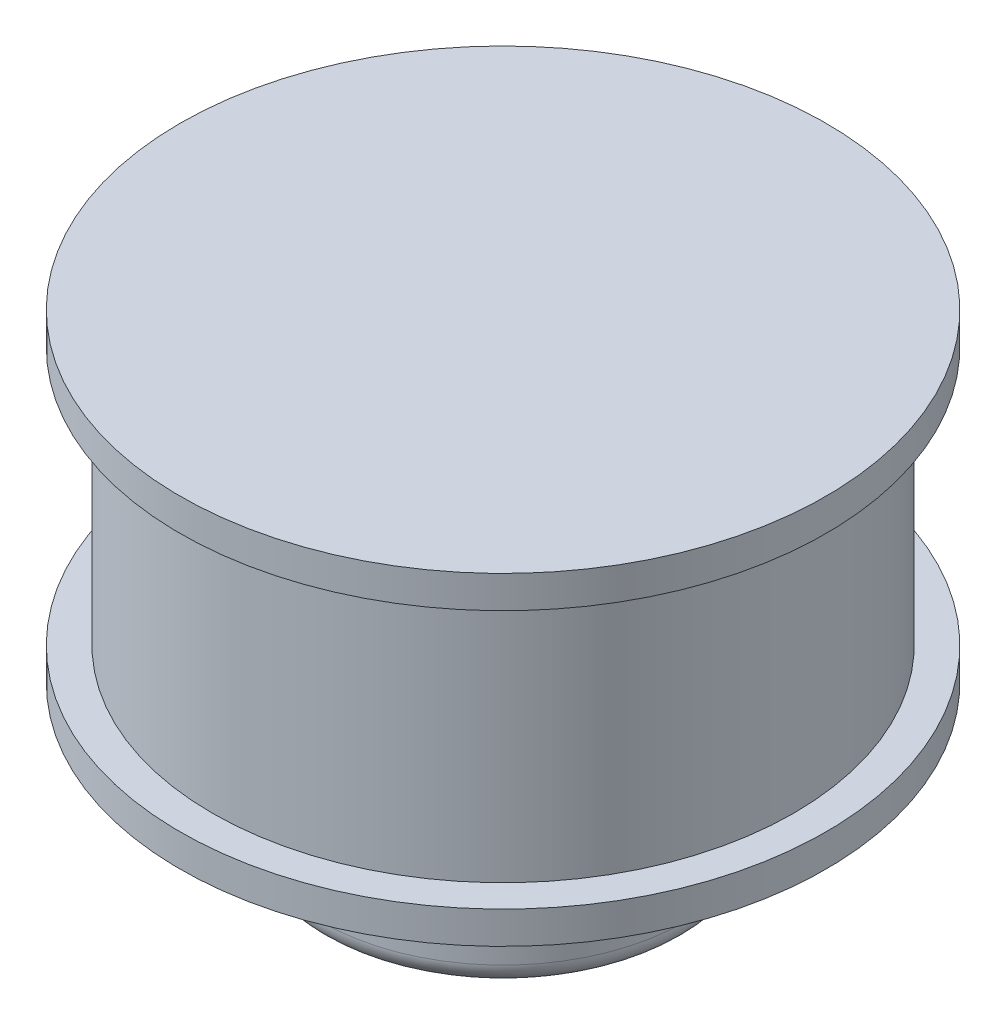
SolidWorks part; units mm, degrees
material "ABS"
ref_plane "Front Plane" through (0, 0, 0) normal (0, 0, 1) x (1, 0, 0)
ref_plane "Top Plane" through (0, 0, 0) normal (0, 1, 0) x (1, 0, 0)
ref_plane "Right Plane" through (0, 0, 0) normal (1, 0, 0) x (0, 0, -1)
sketch "Sketch1" plane through (0, 0, 0) normal (0, 0, 1) x (1, 0, 0)
  line L2 (-8.5, -6.35) -> (-8.5, 0)
  line L3 (-8.5, 0) -> (-15, 0)
  line L4 (-15, 0) -> (-15, 1.5)
  line L5 (-15, 1.5) -> (-13.5, 1.5)
  line L6 (-13.5, 1.5) -> (-13.5, 13.5)
  line L7 (-13.5, 13.5) -> (-15, 13.5)
  line L8 (-15, 13.5) -> (-15, 15)
  line L9 (-15, 15) -> (0, 15)
  line L10 (0, 15) -> (0, 7.65)
  line L11 (-4, -6.35) -> (-8.5, -6.35)
  line L12 (-4, 7.65) -> (-4, -6.35)
  line L13 (0, 7.65) -> (-4, 7.65)
  dimension "D1" = 8.5
  dimension "D2" = 1.5
  dimension "D3" = 6.35
  dimension "D4" = 1.5
  dimension "D5" = 4
  dimension "D6" = 14
  dimension "D7" = 15
  dimension "D8" = 15
revolve "Revolve1" add sketch "Sketch1" angle 360 about L10
fillet "Fillet1" radius 1 2 edges at (-8.5, -6.35, 0) (-4, -6.35, 0)
hole_wizard "M3x0.5 Tapped Hole1" positions "Sketch2" profile "Sketch3" tap size "M3x0.5" standard "ANSI Metric" end condition up to next
sketch "Sketch2" plane through (0, 0, 0) normal (0, 0, 1) x (1, 0, 0)
  line L0 (-7.5, -6.35) -> (7.5, -6.35) construction
  point P0 (0, -2.35)
  dimension "D1" = 4
sketch "Sketch3" plane through (0, -2.35, 0) normal (1, 0, 0) x (0, 1, 0)
  line L0 (0, 0) -> (0, 8.5)
  line L1 (0, 8.5) -> (1.25, 8.5)
  line L2 (1.25, 8.5) -> (1.25, 0)
  line L5 (1.25, 0) -> (0, 0)
  line L11 (0, -6.35) -> (0, 107.95) construction
  dimension "Thru Tap Drill Dia." = 2.5
  dimension "Thru Tap Drill Depth" = 8.5
cosmetic thread "Hole Thread1" parameters "D2"=3
